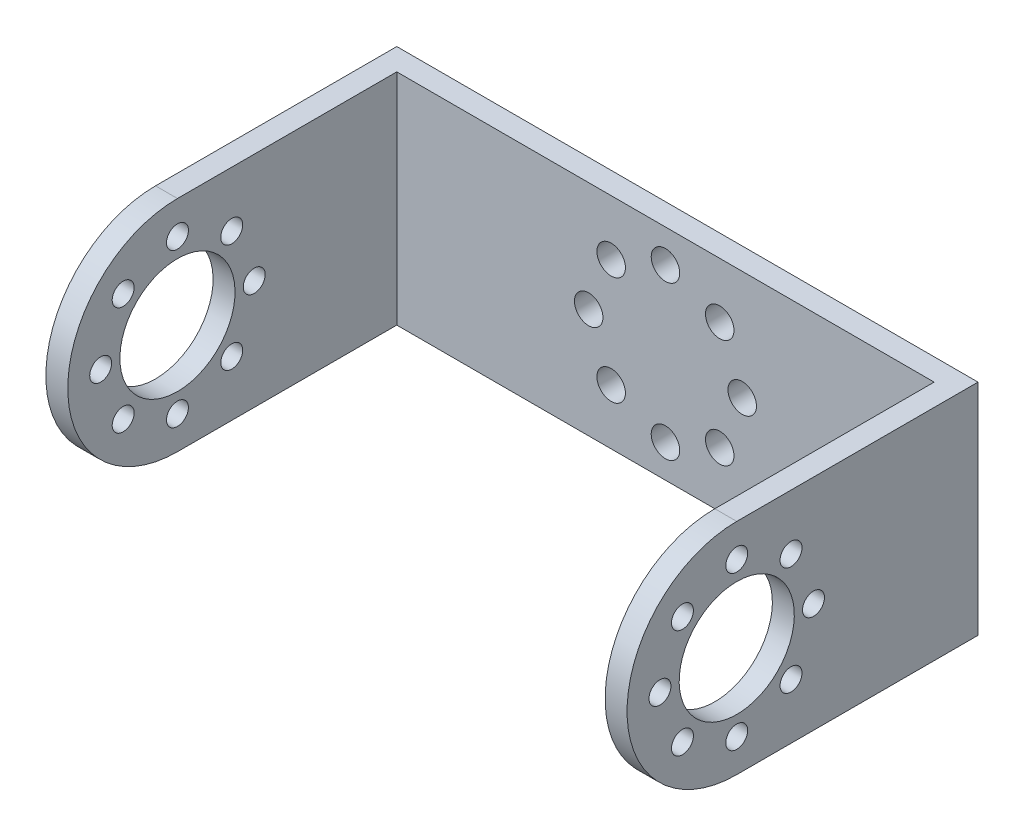
SolidWorks part; units mm, degrees
ref_plane "前基準面" through (0, 0, 0) normal (0, 0, 1) x (1, 0, 0)
ref_plane "上基準面" through (0, 0, 0) normal (0, 1, 0) x (1, 0, 0)
ref_plane "右基準面" through (0, 0, 0) normal (1, 0, 0) x (0, 0, -1)
sketch "草圖1" plane through (0, 0, 0) normal (0, 0, 1) x (1, 0, 0)
  line L1 (-26.5, 10) -> (26.5, 10)
  line L2 (-26.5, 10) -> (-26.5, -10)
  line L3 (-26.5, -10) -> (26.5, -10)
  line L4 (26.5, 10) -> (26.5, -10)
  line L5 (-26.5, 10) -> (26.5, -10) construction
  line L6 (-26.5, -10) -> (26.5, 10) construction
  point P0 (0, 0)
  dimension "D1" = 20
  dimension "D2" = 53
extrude "填料-伸長1" add sketch "草圖1" along normal blind 2
sketch "草圖2" plane through (0, 0, 2) normal (0, 0, 1) x (1, 0, 0)
  line L0 (-26.5, -10) -> (26.5, -10) construction
  line L1 (-26.5, 10) -> (-24.5, 10)
  line L2 (-26.5, 10) -> (-26.5, -10)
  line L3 (-26.5, -10) -> (-24.5, -10)
  line L4 (-24.5, 10) -> (-24.5, -10)
  dimension "D1" = 2
extrude "填料-伸長2" add sketch "草圖2" along normal blind 30
sketch "草圖3" plane through (-24.5, 0, 0) normal (1, 0, 0) x (0, 0, -1)
  line L0 (-22, 10) -> (-22, -10) construction
  line L1 (-32, 10) -> (-2, 10) construction
  line L2 (-32, -10) -> (-2, -10) construction
  line L3 (-32, -10) -> (-32, 10) construction
  arc A0 (-22, -10) -> (-22, 10) centre (-22, 0) cw
  line M3 (-2, 10) -> (-32, 10)
  line M4 (-32, 10) -> (-32, -10)
  line M5 (-32, -10) -> (-2, -10)
  dimension "D1" = 10
extrude "除料-伸長1" cut sketch "草圖3" against normal blind 30 and the other way through all contours A0 M4 M3 | A0 M5 M4 region at (-24.5, -7.7663, 29.7663) region at (-24.5, 7.7663, 29.7663)
sketch "草圖4" plane through (-26.5, 0, 0) normal (-1, 0, 0) x (0, 0, 1)
  line L0 (0, 0) -> (32, 0) construction
  line L1 (0, 10) -> (0, -10) construction
  line L2 (22, 0) -> (29, 0) construction
  arc A0 (22, -10) -> (22, 10) centre (22, 0) ccw construction
  circle A1 centre (29, 0) radius 1
  circle A2 centre (26.9497, -4.9497) radius 1
  circle A3 centre (22, -7) radius 1
  circle A4 centre (17.0503, -4.9497) radius 1
  circle A5 centre (15, 0) radius 1
  circle A6 centre (17.0503, 4.9497) radius 1
  circle A7 centre (22, 7) radius 1
  circle A8 centre (26.9497, 4.9497) radius 1
  circle A9 centre (22, 0) radius 5.25
  point P7 (22, 0)
  dimension "D2" = 2
  dimension "D5" = 10.5
  dimension "D1" = 10
  dimension "D3" = 7
  dimension "D4" = 8
extrude "除料-伸長2" cut sketch "草圖4" against normal up to next
mirror "鏡射1" about plane through (0, 0, 0) normal (1, 0, 0) of "除料-伸長2", "除料-伸長1", "填料-伸長2"
sketch "草圖5" plane through (0, 0, 0) normal (0, 0, -1) x (-1, 0, 0)
  line L0 (-26.5, 0) -> (26.5, 0) construction
  line L1 (-26.5, -10) -> (-26.5, 10) construction
  line L2 (26.5, 10) -> (26.5, -10) construction
  circle A0 centre (-7, 0) radius 1.3
  circle A1 centre (-4.9497, 4.9497) radius 1.3
  circle A2 centre (0, 7) radius 1.3
  circle A3 centre (4.9497, 4.9497) radius 1.3
  circle A4 centre (7, 0) radius 1.3
  circle A5 centre (4.9497, -4.9497) radius 1.3
  circle A6 centre (0, -7) radius 1.3
  circle A7 centre (-4.9497, -4.9497) radius 1.3
  point P6 (0, 0)
  point P11 (0, 0)
  point P12 (0, 7)
  point P26 (0, 0)
  dimension "D1" = 2.6
  dimension "D2" = 7
  dimension "D3" = 8
extrude "除料-伸長3" cut sketch "草圖5" against normal through all
